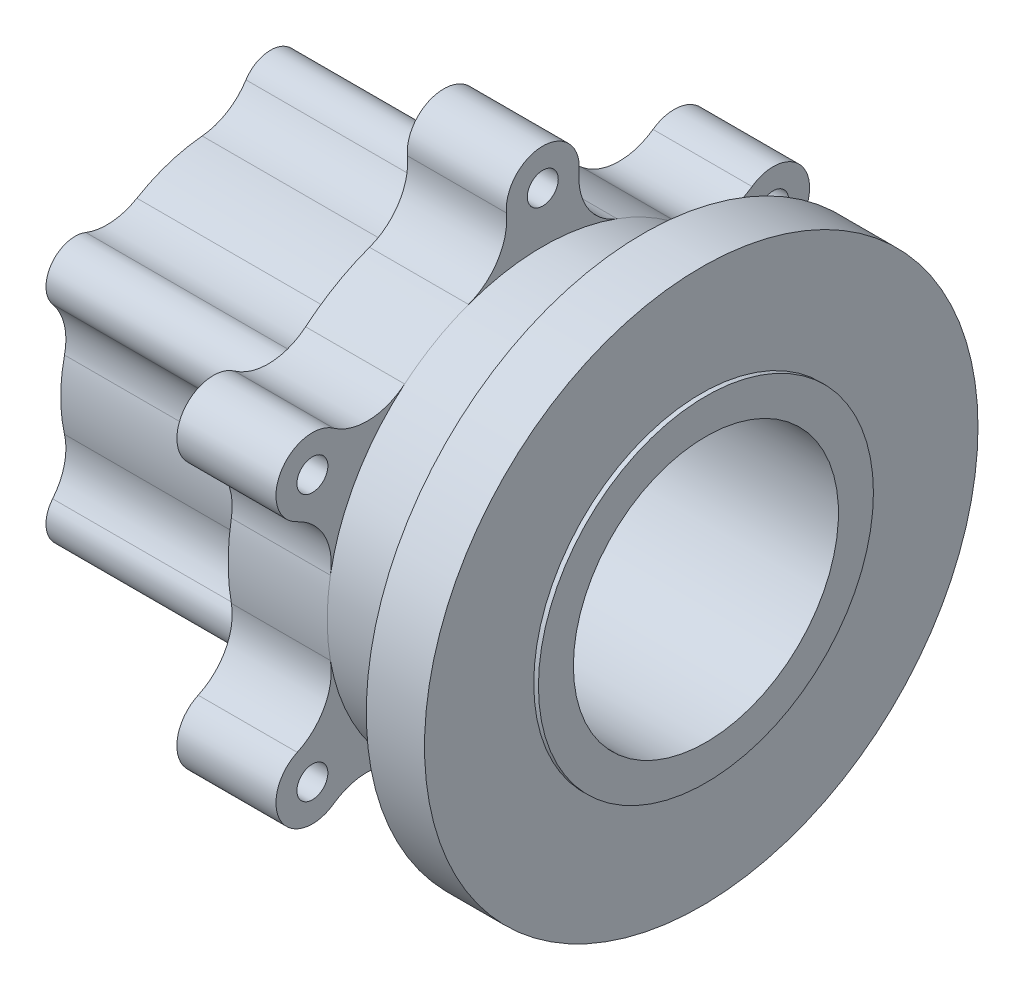
SolidWorks part; units mm, degrees
ref_plane "Front Plane" through (0, 0, 0) normal (1, 0, 0) x (0, 1, 0)
ref_plane "Top Plane" through (0, 0, 0) normal (0, 0, 1) x (0, 1, 0)
ref_plane "Right Plane" through (0, 0, 0) normal (0, 1, 0) x (-1, 0, 0)
sketch "Sketch1" plane through (0, 0, 0) normal (0, 1, 0) x (-1, 0, 0)
  line L0 (0, 68.99) -> (6.35, 68.99)
  line L1 (0, 0) -> (71.12, 0)
  line L2 (0, 0) -> (0, 157.48)
  line L3 (0, 157.48) -> (71.12, 157.48) construction
  line L4 (71.12, 0) -> (71.12, 157.48)
  line L5 (6.35, 68.99) -> (6.35, 149.987)
  line L6 (6.35, 149.987) -> (13.843, 157.48)
  line L7 (63.627, 157.48) -> (71.12, 149.987)
  line L8 (-21.844, 60.325) -> (-21.844, 36.5125)
  line L9 (0, 0) -> (-20.32, 0)
  line L10 (0, 0) -> (0, 46.99)
  line L11 (0, 46.99) -> (-20.32, 46.99)
  line L12 (-20.32, 0) -> (-20.32, 46.99)
  line L13 (71.12, 0) -> (83.82, 0) construction
  line L14 (71.12, 0) -> (71.12, 14.9987) construction
  line L15 (71.12, 14.9987) -> (83.82, 14.9987) construction
  line L16 (83.82, 0) -> (83.82, 14.9987) construction
  line L17 (83.82, 0) -> (96.52, 0) construction
  line L18 (83.82, 0) -> (83.82, 24.13) construction
  line L19 (83.82, 24.13) -> (96.52, 24.13) construction
  line L20 (96.52, 0) -> (96.52, 24.13) construction
  line L21 (-20.32, 0) -> (-35.56, 0)
  line L22 (-20.32, 0) -> (-20.32, 36.5125)
  line L23 (-20.32, 36.5125) -> (-35.56, 36.5125)
  line L24 (-35.56, 0) -> (-35.56, 36.5125)
  line L25 (-21.844, 36.5125) -> (-34.544, 36.5125)
  line L26 (-34.544, 36.5125) -> (-34.544, 60.325)
  line L27 (-34.544, 60.325) -> (-21.844, 60.325)
  line L28 (6.35, 68.99) -> (71.12, 68.99)
  dimension "D1" = 157.48
  dimension "D2" = 71.12
  dimension "D3" = 12.7
  dimension "D4" = 12.7
  dimension "D5" = 14.9987
  dimension "D6" = 24.13
  dimension "D7" = 20.32
  dimension "D8" = 45
  dimension "D9" = 45
  dimension "D10" = 6.35
  dimension "D11" = 46.99
  dimension "D13" = 36.5125
  dimension "D14" = 132.08
  dimension "D12" = 49.784
  dimension "D16" = 60.325
  dimension "D17" = 12.7
  dimension "D18" = 36.5125
  dimension "D19" = 68.99
  dimension "D15" = 1.016
revolve "Revolve1" add sketch "Sketch1" angle 360 about L1 region at (-35.56, 0, 34.495) region at (10.16, 0, 23.495) region at (27.94, 0, 18.2562)
revolve "Revolve2" add sketch "Sketch1<3>" angle 360 about L1 region at (28.194, 0, 48.4187)
sketch "Sketch1<3>" plane through (0, 0, 0) normal (0, 1, 0) x (-1, 0, 0) same geometry as "Sketch1"
sketch "Sketch2" plane through (-71.12, 0, 0) normal (-1, 0, 0) x (0, -1, 0)
  line L1 (0, -38.1) -> (36.2353, -11.7735)
  line L2 (36.2353, -11.7735) -> (22.3946, 30.8235)
  line L3 (22.3946, 30.8235) -> (-22.3946, 30.8235)
  line L4 (-22.3946, 30.8235) -> (-36.2353, -11.7735)
  line L5 (-36.2353, -11.7735) -> (0, -38.1)
  circle A0 centre (0, 0) radius 38.1
  circle A1 centre (0, 0) radius 68.99
  circle A3 centre (0, 0) radius 30.8235 construction
  circle A5 centre (0, 0) radius 68.99
  dimension "D2" = 76.2
  dimension "D1" = 0
sketch "Sketch3" plane through (-71.12, 0, 0) normal (-1, 0, 0) x (0, -1, 0)
  circle A0 centre (-22.3946, 30.8235) radius 3.3734
  circle A1 centre (22.3946, 30.8235) radius 3.3734
  circle A2 centre (36.2353, -11.7735) radius 3.3734
  circle A3 centre (0, -38.1) radius 3.3734
  circle A4 centre (-36.2353, -11.7735) radius 3.3734
  point P0 (-36.2353, -11.7735)
  point P2 (0, -38.1)
  point P4 (36.2353, -11.7735)
  point P6 (22.3946, 30.8235)
  point P8 (-22.3946, 30.8235)
  dimension "D1" = 6.7469
extrude "Cut-Extrude1" cut sketch "Sketch3" against normal blind 13.97
sketch "Sketch4" plane through (0, 0, 0) normal (1, 0, 0) x (0, 1, 0)
  line L0 (28.995, -50.2208) -> (57.99, 0)
  line L1 (57.99, 0) -> (28.995, 50.2208)
  line L2 (28.995, 50.2208) -> (-28.995, 50.2208)
  line L3 (-28.995, 50.2208) -> (-57.99, 0)
  line L4 (-57.99, 0) -> (-28.995, -50.2208)
  line L5 (-28.995, -50.2208) -> (28.995, -50.2208)
  circle A0 centre (0, 0) radius 50.2208 construction
  circle A1 centre (0, 0) radius 68.99
  circle A2 centre (0, 0) radius 68.99
  circle A3 centre (28.995, 50.2208) radius 3.3734
  dimension "D3" = 6.7469
  dimension "D2" = 115.98
  dimension "D1" = 0
sketch "Sketch5" plane through (0, 0, 0) normal (1, 0, 0) x (0, 1, 0)
  circle A0 centre (28.995, 50.2208) radius 3.3734 construction
  circle A1 centre (28.995, 50.2208) radius 3.3734
  circle A2 centre (-28.995, 50.2208) radius 3.3734
  circle A3 centre (-57.99, 0) radius 3.3734
  circle A4 centre (-28.995, -50.2208) radius 3.3734
  circle A5 centre (28.995, -50.2208) radius 3.3734
  circle A6 centre (57.99, 0) radius 3.3734
  point P0 (28.995, -50.2208)
  point P2 (57.99, 0)
  point P4 (28.995, 50.2208)
  point P9 (-28.995, -50.2208)
  point P11 (-57.99, 0)
  point P13 (-28.995, 50.2208)
extrude "Cut-Extrude2" cut sketch "Sketch5" against normal blind 13.97
sketch "Sketch10" plane through (0, 0, 0) normal (1, 0, 0) x (0, 1, 0)
  line L0 (-28.995, 50.2208) -> (0, 0) construction
  circle A0 centre (0, -38.1) radius 3.3734 construction
  circle A1 centre (-36.2353, -11.7735) radius 3.3734 construction
  circle A2 centre (-22.3946, 30.8235) radius 3.3734 construction
  circle A3 centre (36.2353, -11.7735) radius 3.3734 construction
  circle A4 centre (22.3946, 30.8235) radius 3.3734 construction
  circle A5 centre (0, -38.1) radius 3.3734
  circle A6 centre (-36.2353, -11.7735) radius 3.3734
  circle A7 centre (-22.3946, 30.8235) radius 3.3734
  circle A8 centre (36.2353, -11.7735) radius 3.3734
  circle A9 centre (22.3946, 30.8235) radius 3.3734
  circle A10 centre (57.99, 0) radius 3.3734 construction
  circle A11 centre (28.995, -50.2208) radius 3.3734 construction
  circle A12 centre (-28.995, -50.2208) radius 3.3734 construction
  circle A13 centre (-57.99, 0) radius 3.3734 construction
  circle A14 centre (-28.995, 50.2208) radius 3.3734 construction
  circle A15 centre (28.995, 50.2208) radius 3.3734 construction
  circle A16 centre (57.99, 0) radius 3.3734
  circle A17 centre (28.995, -50.2208) radius 3.3734
  circle A18 centre (-28.995, -50.2208) radius 3.3734
  circle A19 centre (-57.99, 0) radius 3.3734
  circle A20 centre (-28.995, 50.2208) radius 3.3734
  circle A21 centre (28.995, 50.2208) radius 3.3734
  circle A22 centre (0, 0) radius 68.99 construction
  circle A23 centre (0, 0) radius 46.99 construction
  circle A24 centre (0, 0) radius 68.99
  circle A25 centre (0, 0) radius 46.99
  circle A26 centre (-28.995, 50.2208) radius 7.9454
  arc A27 (-35.4699, 45.6159) -> (-36.0706, 30.1159) centre (-45.8195, 38.2554) cw
  arc A28 (-21.7696, 53.5258) -> (-8.0458, 46.2961) centre (-10.2204, 58.8085) ccw
  arc A29 (35.4699, 45.6159) -> (36.0706, 30.1159) centre (45.8195, 38.2554) ccw
  circle A30 centre (28.995, 50.2208) radius 7.9454
  arc A31 (21.7696, 53.5258) -> (8.0458, 46.2961) centre (10.2204, 58.8085) cw
  arc A32 (57.2395, -7.9099) -> (44.1165, -16.1801) centre (56.0399, -20.5531) ccw
  circle A33 centre (57.99, 0) radius 7.9454
  arc A34 (57.2395, 7.9099) -> (44.1165, 16.1801) centre (56.0399, 20.5531) cw
  arc A35 (21.7696, -53.5258) -> (8.0458, -46.2961) centre (10.2204, -58.8085) ccw
  circle A36 centre (28.995, -50.2208) radius 7.9454
  arc A37 (35.4699, -45.6159) -> (36.0706, -30.1159) centre (45.8195, -38.2554) cw
  arc A38 (-35.4699, -45.6159) -> (-36.0706, -30.1159) centre (-45.8195, -38.2554) ccw
  circle A39 centre (-28.995, -50.2208) radius 7.9454
  arc A40 (-21.7696, -53.5258) -> (-8.0458, -46.2961) centre (-10.2204, -58.8085) cw
  arc A41 (-57.2395, 7.9099) -> (-44.1165, 16.1801) centre (-56.0399, 20.5531) ccw
  circle A42 centre (-57.99, 0) radius 7.9454
  arc A43 (-57.2395, -7.9099) -> (-44.1165, -16.1801) centre (-56.0399, -20.5531) cw
  point P87 (0, 0)
  circle M12 centre (0, 0) radius 68.99
  circle M13 centre (0, 0) radius 46.99
  dimension "D1" = 4.572
  dimension "D2" = 12.7
  dimension "D3" = 6
extrude "Cut-Extrude3" cut sketch "Sketch10" against normal through all contours A43 A42 A41 A27 A26 A28 A25 A31 A30 A29 A34 A33 A32 A37 A36 A35 A40 A39 A38 M12 M13 region at (0, -67.0387, 0)
ref_plane "Plane1" through (-21.59, 0, 0) normal (1, 0, 0) x (0, 0, -1)
sketch "Sketch12" plane through (-21.59, 0, 0) normal (1, 0, 0) x (0, 0, -1)
  circle A0 centre (0, 0) radius 46.99 construction
  circle A1 centre (0, 0) radius 46.99
  circle A2 centre (0, 0) radius 65.9354
  arc A3 (-7.9099, -57.2395) -> (7.9099, -57.2395) centre (0, -57.99) ccw construction
extrude "Cut-Extrude6" cut sketch "Sketch12" against normal through all
sketch "Sketch13" plane through (-71.12, 0, 0) normal (-1, 0, 0) x (0, -1, 0)
  line L0 (0, 0) -> (0, 28.8925) construction
  line L1 (0, 0) -> (-26.1271, 35.9608) construction
  circle A0 centre (0, 0) radius 36.5125 construction
  circle A1 centre (0, 0) radius 36.5125 construction
  circle A2 centre (0, 0) radius 46.99 construction
  circle A3 centre (22.3946, 30.8235) radius 3.3734 construction
  circle A4 centre (-22.3946, 30.8235) radius 3.3734 construction
  circle A5 centre (0, 0) radius 46.99
  circle A6 centre (22.3946, 30.8235) radius 3.3734
  circle A7 centre (-22.3946, 30.8235) radius 3.3734
  circle A8 centre (0, 0) radius 28.8925
  circle A9 centre (0, 0) radius 33.9725
  circle A10 centre (-22.3946, 30.8235) radius 6.35
  arc A11 (-18.3568, 35.7244) -> (-7.4835, 33.138) centre (-10.281, 45.5261) ccw
  circle A12 centre (22.3946, 30.8235) radius 6.35
  arc A13 (18.3568, 35.7244) -> (7.4835, 33.138) centre (10.281, 45.5261) cw
  arc A14 (39.6485, -6.4189) -> (33.8287, 3.123) centre (46.4749, 4.2905) cw
  arc A15 (28.3034, 28.4978) -> (29.2036, 17.3574) centre (40.1208, 23.8462) ccw
  circle A16 centre (36.2353, -11.7735) radius 6.35
  arc A17 (6.1473, -39.6915) -> (13.4238, -31.2079) centre (18.442, -42.8744) cw
  arc A18 (35.8492, -18.1118) -> (25.5323, -22.4105) centre (35.0771, -30.7883) ccw
  circle A19 centre (0, -38.1) radius 6.35
  arc A20 (-35.8492, -18.1118) -> (-25.5323, -22.4105) centre (-35.0771, -30.7883) cw
  arc A21 (-6.1473, -39.6915) -> (-13.4238, -31.2079) centre (-18.442, -42.8744) ccw
  circle A22 centre (-36.2353, -11.7735) radius 6.35
  arc A23 (-28.3034, 28.4978) -> (-29.2036, 17.3574) centre (-40.1208, 23.8462) cw
  arc A24 (-39.6485, -6.4189) -> (-33.8287, 3.123) centre (-46.4749, 4.2905) ccw
  circle A25 centre (-22.3946, 30.8235) radius 6.35
  point P57 (0, 0)
  circle M8 centre (0, 0) radius 46.99
  dimension "D1" = 7.62
  dimension "D2" = 5.08
  dimension "D3" = 44.45
  dimension "D4" = 12.7
  dimension "D5" = 5
extrude "Cut-Extrude7" cut sketch "Sketch13" against normal up to surface (49.53 mm away) contours A22 A24 A9 A23 A10 A11 A13 A12 A15 A14 A16 A18 A17 A19 A21 A20 M8 region at (-71.12, 45.6609, 0) up to face at (-21.59, 26.4329, 45.783)
extrude "Cut-Extrude8" cut sketch "Sketch13<3>" against normal through all contours A8 region at (-71.12, 0, 0)
sketch "Sketch13<3>" plane through (-71.12, 0, 0) normal (-1, 0, 0) x (0, -1, 0) same geometry as "Sketch13"
ref_plane "Plane2" through (0, 0, 0) normal (1, 0, 0) x (0, 0, -1)
split line "Split Line7"
equation "\"D9@Sketch1\"=\"D8@Sketch1\""
equation "\"D19@Sketch1\"=115.98mm-\"D11@Sketch1\""
